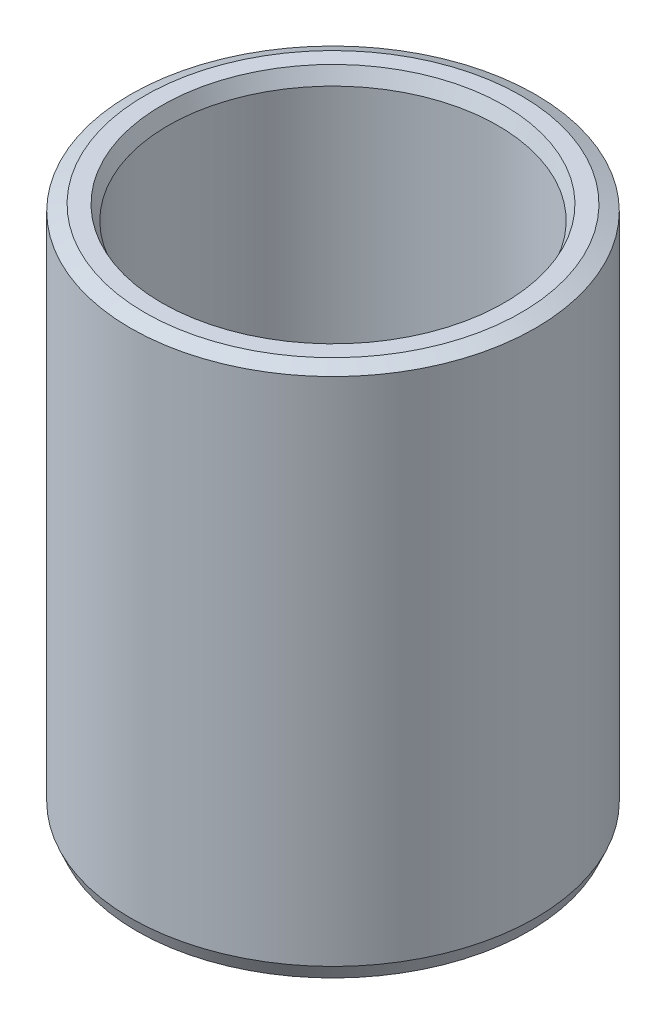
SolidWorks part; units mm, degrees
ref_plane "Front Plane" through (0, 0, 0) normal (0, 0, 1) x (1, 0, 0)
ref_plane "Top Plane" through (0, 0, 0) normal (0, 1, 0) x (1, 0, 0)
ref_plane "Right Plane" through (0, 0, 0) normal (1, 0, 0) x (0, 0, -1)
sketch "Sketch1" plane through (0, 0, 0) normal (0, 1, 0) x (1, 0, 0)
  circle A0 centre (0, 0) radius 55
  dimension "SLEEVE_OD" = 110
extrude "Boss-Extrude1" add sketch "Sketch1" along normal blind 144.3746
sketch "Sketch2" plane through (0, 0, 0) normal (0, 1, 0) x (1, 0, 0)
  circle A0 centre (0, 0) radius 44.7992
  dimension "BORE_D" = 89.5984
extrude "Cut-Extrude1" cut sketch "Sketch2" along normal through all
chamfer "Chamfer1" distance 1.6882 angle 66.624 4 edges at (0, 144.3746, 44.7992) (0, 0, 44.7992) (0, 0, 55) (0, 144.3746, 55) first distance on face at (0, 144.3746, 44.7992) first distance on face at (0, 0, 44.7992) first distance on face at (0, 144.3746, 55)
